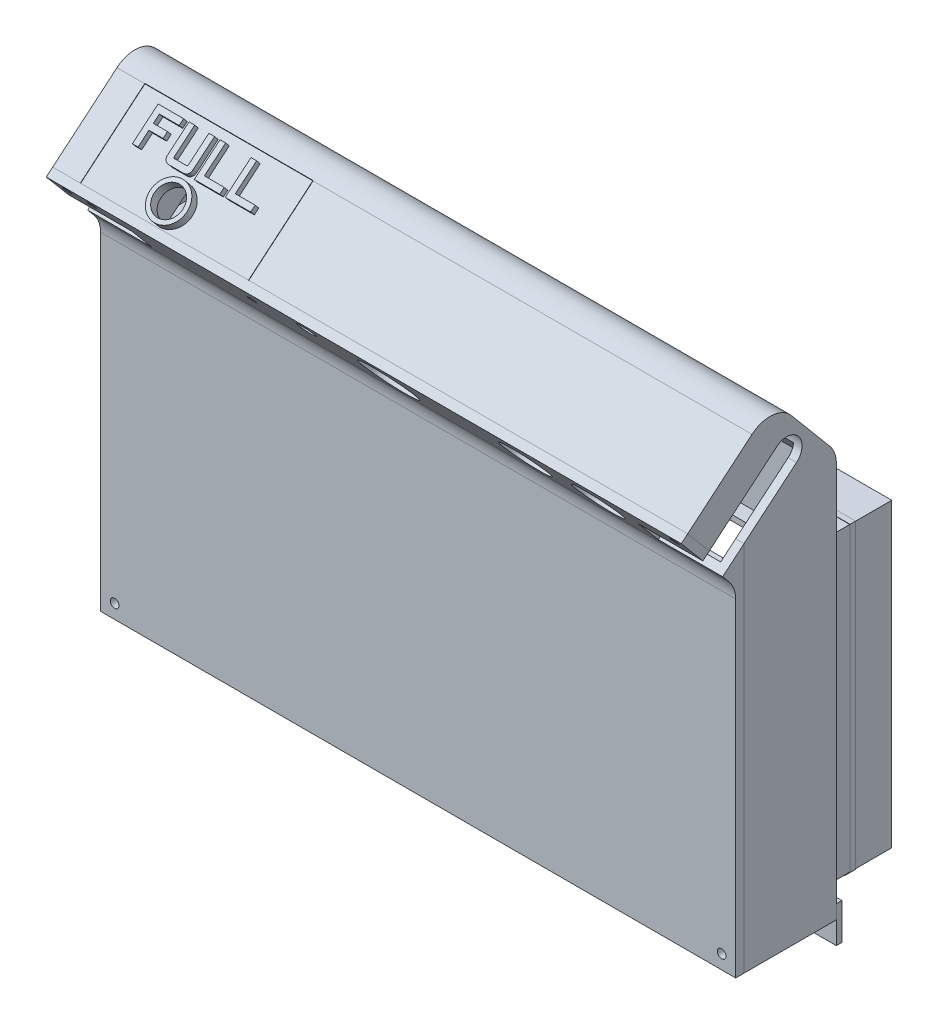
SolidWorks part; units mm, degrees
note: The reader was unsure of these and kept them because the rebuilt part matched: shared geometry of "스케치1<2>", "스케치2<3>", "스케치27<2>".
ref_plane "정면" through (0, 0, 0) normal (0, 0, 1) x (1, 0, 0)
ref_plane "윗면" through (0, 0, 0) normal (0, 1, 0) x (1, 0, 0)
ref_plane "우측면" through (0, 0, 0) normal (1, 0, 0) x (0, 0, -1)
sketch "스케치1" plane through (0, 0, 0) normal (0, 0, 1) x (1, 0, 0)
  line L5 (-104.9346, 72.3999) -> (122.0654, 72.3999)
  line L6 (-104.9346, 72.3999) -> (-104.9346, -72.6001)
  line L7 (-104.9346, -72.6001) -> (122.0654, -72.6001)
  line L8 (122.0654, 72.3999) -> (122.0654, -72.6001)
  line L9 (-101.9346, 69.3999) -> (119.0654, 69.3999)
  line L10 (-101.9346, 69.3999) -> (-101.9346, -69.6001)
  line L11 (-101.9346, -69.6001) -> (119.0654, -69.6001)
  line L12 (119.0654, 69.3999) -> (119.0654, -69.6001)
  dimension "D1" = 3
  dimension "D2" = 3
  dimension "D3" = 3
  dimension "D4" = 3
  dimension "D5" = 227
  dimension "D6" = 145
extrude "보스-돌출1" add sketch "스케치1" along normal blind 30
extrude "보스-돌출2" add sketch "스케치1<2>" against normal blind 3 contours L12 L9 L10 L11 | L8 L5 L6 L7 L9 L12 L11 L10
sketch "스케치1<2>" plane through (0, 0, 0) normal (0, 0, 1) x (1, 0, 0) same geometry as "스케치1"
sketch "스케치2" plane through (122.0654, 0, 0) normal (1, 0, 0) x (0, 0, -1)
  line L0 (3, 72.3999) -> (-19.4976, 99.2114)
  line L1 (-19.4976, 99.2114) -> (-21.7957, 97.2831)
  line L2 (-21.7957, 97.2831) -> (-0.9162, 72.3999)
  line L3 (-30, 72.3999) -> (3, 72.3999) construction
  line L4 (3, 72.3999) -> (3, -72.6001) construction
  line L5 (-11.2248, 76.1287) -> (-39.8222, 52.1327)
  line L6 (-39.8222, 52.1327) -> (-46.8928, 60.5592)
  line L7 (-46.8928, 60.5592) -> (-18.2955, 84.5552)
  line L8 (3, 72.3999) -> (-27.6418, 46.6884)
  line L9 (-19.4976, 99.2114) -> (-50.1393, 73.4999)
  line L10 (-50.1393, 73.4999) -> (-27.6418, 46.6884)
  circle A0 centre (-14.7602, 80.3419) radius 5.5
  line M5 (3, 72.3999) -> (-30, 72.3999)
  line M6 (-30, 72.3999) -> (-30, -72.6001)
  dimension "D3" = 11
  dimension "D5" = 17.5
  dimension "D6" = 8.5
  dimension "D7" = 5.5
  dimension "D1" = 3
  dimension "D2" = 140
  dimension "D4" = 35
  dimension "D8" = 11
  dimension "D9" = 40
  dimension "D10" = 90
extrude "보스-돌출3" add sketch "스케치2" against normal up to vertex contours A0 L2 L9 L10 L7 | L10 L8 L5 M6 M5 | A0 L5 L2 M5 | L1 L2 L0 M5
extrude "컷-돌출1" cut sketch "스케치2<3>" against normal up to vertex (227 mm away) contours A0 L7 L10 L5 M6 M5 | L5 M5 M6 | A0 | L10 L7 L6 L5 up to point (-104.9346, 99.2114, 19.4976)
sketch "스케치2<3>" plane through (122.0654, 0, 0) normal (1, 0, 0) x (0, 0, -1) same geometry as "스케치2"
sketch "스케치3" plane through (0, 41.0088, 34.4104) normal (0, -0.766, -0.6428) x (1, 0, 0)
  line L8 (-101.9346, -8.8359) -> (-101.9346, -44.1687)
  line L9 (-101.9346, -44.1687) -> (119.0654, -44.1687)
  line L10 (119.0654, -44.1687) -> (119.0654, -8.8359)
  line L11 (119.0654, -8.8359) -> (-101.9346, -8.8359)
  line L12 (-101.9346, -8.8359) -> (-101.9346, -44.1687)
  line L13 (-101.9346, -44.1687) -> (119.0654, -44.1687)
  line L14 (119.0654, -44.1687) -> (119.0654, -8.8359)
  line L15 (119.0654, -8.8359) -> (-101.9346, -8.8359)
  dimension "D1" = 0
extrude "컷-돌출2" cut sketch "스케치3" against normal blind 33
sketch "스케치4" plane through (0, 28.3911, -33.8352) normal (0, -0.6428, 0.766) x (1, 0, 0)
  line L0 (-101.9346, 86.5331) -> (-101.9346, 74.9777) construction
  line L1 (-81.9346, 86.5331) -> (99.0654, 86.5331)
  line L2 (-81.9346, 86.5331) -> (-81.9346, 53.5331)
  line L3 (-81.9346, 53.5331) -> (99.0654, 53.5331)
  line L4 (99.0654, 86.5331) -> (99.0654, 53.5331)
  line L5 (119.0654, 86.5331) -> (119.0654, 74.9777) construction
  dimension "D1" = 20
  dimension "D2" = 20
extrude "보스-돌출4" add sketch "스케치4" against normal up to vertex (4.6672 mm away) up to point (-104.9346, 99.2114, 19.4976)
sketch "스케치5" plane through (0, 5.6796, -6.7687) normal (0, -0.6428, 0.766) x (1, 0, 0)
  line L0 (122.0654, -36.3313) -> (122.0654, 65.5331) construction
  line L1 (-104.9346, 88.5331) -> (122.0654, 88.5331)
  line L2 (-104.9346, 88.5331) -> (-104.9346, 57.8136)
  line L3 (-104.9346, 57.8136) -> (122.0654, 57.8136)
  line L5 (-81.9346, 74.9777) -> (-81.9346, 67.0886) construction
  line L6 (-104.9346, 76.5331) -> (-81.9346, 76.5331)
  line L7 (-104.9346, 76.5331) -> (-104.9346, 65.5331)
  line L8 (-104.9346, 65.5331) -> (-81.9346, 65.5331)
  line L9 (-81.9346, 76.5331) -> (-81.9346, 65.5331)
  line L10 (99.0654, 67.0886) -> (99.0654, 74.9777) construction
  line L11 (122.0654, 76.5331) -> (99.0654, 76.5331)
  line L12 (122.0654, 76.5331) -> (122.0654, 65.5331)
  line L13 (122.0654, 65.5331) -> (99.0654, 65.5331)
  line L14 (99.0654, 76.5331) -> (99.0654, 65.5331)
  line L15 (-104.9346, 88.5331) -> (-104.9346, 76.5331)
  line L16 (-104.9346, 76.5331) -> (-81.9346, 76.5331)
  line L17 (-81.9346, 76.5331) -> (-81.9346, 65.5331)
  line L23 (-104.9346, 65.5331) -> (-104.9346, -36.3313) construction
  line L24 (-104.9346, 65.5331) -> (-81.9346, 65.5331)
  line L25 (122.0654, 76.5331) -> (99.0654, 76.5331)
  line L26 (99.0654, 65.5331) -> (99.0654, 76.5331)
  line L27 (99.0654, 65.5331) -> (122.0654, 65.5331)
  line L28 (122.0654, 88.5331) -> (122.0654, 57.8136)
  line L29 (119.0654, 76.5331) -> (122.0654, 76.5331) construction
  circle A0 centre (-99.9346, 84.5331) radius 1.55
  circle A1 centre (117.0654, 84.5331) radius 1.55
  line M3 (119.0654, 86.5331) -> (119.0654, 76.5331)
  line M4 (119.0654, 76.5331) -> (122.0654, 76.5331)
  line M5 (122.0654, 76.5331) -> (122.0654, 88.5331)
  line M6 (122.0654, 88.5331) -> (-104.9346, 88.5331)
  line M7 (-104.9346, 88.5331) -> (-104.9346, 76.5331)
  line M8 (-104.9346, 76.5331) -> (-101.9346, 76.5331)
  line M9 (-101.9346, 76.5331) -> (-101.9346, 86.5331)
  line M10 (-101.9346, 86.5331) -> (119.0654, 86.5331)
  dimension "D1" = 3.1
  dimension "D2" = 3.1
sketch "스케치6" plane through (0, 28.3911, -33.8352) normal (0, -0.6428, 0.766) x (1, 0, 0)
  line L1 (-101.9346, 86.5331) -> (-97.9346, 86.5331)
  line L2 (-101.9346, 86.5331) -> (-101.9346, 82.5331)
  line L3 (-101.9346, 82.5331) -> (-97.9346, 82.5331)
  line L4 (-97.9346, 86.5331) -> (-97.9346, 82.5331)
  line L5 (119.0654, 86.5331) -> (115.0654, 86.5331)
  line L6 (119.0654, 86.5331) -> (119.0654, 82.5331)
  line L7 (119.0654, 82.5331) -> (115.0654, 82.5331)
  line L8 (115.0654, 86.5331) -> (115.0654, 82.5331)
  circle A0 centre (-99.9346, 84.5331) radius 1.5
  circle A1 centre (117.0654, 84.5331) radius 1.5
  dimension "D3" = 3
  dimension "D4" = 2
  dimension "D5" = 2
  dimension "D8" = 3
  dimension "D9" = 2
  dimension "D10" = 2
  dimension "D1" = 4
  dimension "D2" = 4
  dimension "D6" = 4
  dimension "D7" = 4
extrude "보스-돌출6" add sketch "스케치5" along normal blind 3 separate body contours L28 L13 L14 L11 L6 L9 L8 L2 L3 A1 A0 M3 M10 M9 | M10 M3 M4 M5 M6 M7 M8 M9
extrude "보스-돌출7" add sketch "스케치6" along normal up to vertex
sketch "스케치7" plane through (0, 0, 30) normal (0, 0, 1) x (1, 0, 0)
  line L0 (-101.9346, -69.6001) -> (119.0654, -69.6001) construction
  line L1 (-104.9346, 52.2199) -> (122.0654, 52.2199)
  line L2 (-104.9346, 52.2199) -> (-104.9346, -72.6001)
  line L3 (-104.9346, -72.6001) -> (122.0654, -72.6001)
  line L4 (122.0654, 52.2199) -> (122.0654, -72.6001)
  line L5 (-101.9346, 60.3745) -> (-101.9346, -69.6001) construction
  line L6 (119.0654, -69.6001) -> (119.0654, 69.3999) construction
  line L7 (-101.9346, -69.6001) -> (119.0654, -69.6001) construction
  circle A0 centre (-99.9346, -67.6001) radius 1.55
  circle A1 centre (117.0654, -67.6001) radius 1.55
  dimension "D1" = 3.1
  dimension "D2" = 3.1
  dimension "D3" = 2
  dimension "D4" = 2
  dimension "D5" = 2
  dimension "D6" = 2
extrude "보스-돌출8" add sketch "스케치7" along normal blind 3
sketch "스케치8" plane through (-104.9346, 0, 0) normal (-1, 0, 0) x (0, 0, 1)
  line L0 (30, 60.3745) -> (37.6534, 53.9525)
  line L1 (37.6534, 53.9525) -> (34.1765, 49.8089)
  line L2 (37.6534, 53.9525) -> (33, 48.4069) construction
  line L3 (34.1765, 49.8089) -> (30, 52.2199)
  line L4 (30, 52.2199) -> (30, 60.3745)
sketch "스케치9" plane through (122.0654, 0, 0) normal (1, 0, 0) x (0, 0, -1)
  line L8 (-30, 60.3745) -> (-37.6534, 53.9525)
  line L9 (-37.6534, 53.9525) -> (-34.1765, 49.8089)
  line L10 (-34.1765, 49.8089) -> (-30, 52.2199)
  line L11 (-30, 52.2199) -> (-30, 60.3745)
  line L12 (-30, 60.3745) -> (-37.6534, 53.9525)
  line L13 (-37.6534, 53.9525) -> (-34.1765, 49.8089)
  line L14 (-34.1765, 49.8089) -> (-30, 52.2199)
  line L15 (-30, 52.2199) -> (-30, 60.3745)
  dimension "D1" = 0
extrude "보스-돌출9" add sketch "스케치9" against normal blind 3
extrude "보스-돌출10" add sketch "스케치8" against normal blind 3
sketch "스케치10" plane through (0, 0, -3) normal (0, 0, -1) x (-1, 0, 0)
  line L0 (104.9346, 72.3999) -> (-122.0654, 72.3999) construction
  line L1 (-117.0654, 42.3999) -> (99.9346, 42.3999)
  line L2 (-117.0654, 42.3999) -> (-117.0654, -67.6001)
  line L3 (-117.0654, -67.6001) -> (99.9346, -67.6001)
  line L4 (99.9346, 42.3999) -> (99.9346, -67.6001)
  line L5 (104.9346, -72.6001) -> (-122.0654, -72.6001) construction
  line L6 (-122.0654, 72.3999) -> (-122.0654, -72.6001) construction
  line L7 (104.9346, 72.3999) -> (104.9346, -72.6001) construction
  dimension "D1" = 30
  dimension "D2" = 5
  dimension "D3" = 5
  dimension "D4" = 5
extrude "컷-돌출3" cut sketch "스케치10" against normal blind 3
sketch "스케치11" plane through (0, 5.6796, -6.7687) normal (0, 0.6428, -0.766) x (-1, 0, 0)
  line L0 (-122.0654, 88.5331) -> (104.9346, 88.5331) construction
  line L3 (-122.0654, 76.5331) -> (-122.0654, 88.5331) construction
  circle A0 centre (-8.5654, 74.6831) radius 9.4
  circle A1 centre (-8.5654, 74.6831) radius 11.7
  circle A2 centre (-83.006, 73.9536) radius 8.1
  circle A3 centre (-57.006, 73.9536) radius 8.1
  dimension "D1" = 18.8
  dimension "D2" = 23.4
  dimension "D4" = 113.5
  dimension "D5" = 16.2
  dimension "D6" = 16.2
  dimension "D3" = 13.85
  dimension "D7" = 26
extrude "컷-돌출4" cut sketch "스케치11" against normal blind 3 contours A0 | A3 | A2
sketch "스케치13" plane through (0, 5.6796, -6.7687) normal (0, 0.6428, -0.766) x (-1, 0, 0)
  line L0 (-122.0654, 88.5331) -> (104.9346, 88.5331) construction
  line L2 (34.9346, 88.5331) -> (94.9346, 88.5331)
  line L3 (34.9346, 88.5331) -> (34.9346, 68.5331)
  line L4 (34.9346, 68.5331) -> (94.9346, 68.5331)
  line L5 (94.9346, 88.5331) -> (94.9346, 68.5331)
  line L6 (81.9346, 76.5331) -> (81.9346, 68.5331)
  line L7 (81.9346, 76.5331) -> (81.9346, 65.5331) construction
  line L8 (81.9346, 76.5331) -> (94.9346, 76.5331)
  line L9 (104.9346, 76.5331) -> (81.9346, 76.5331) construction
  circle A0 centre (16.4346, 81.5331) radius 3.05
  circle A1 centre (-8.5654, 74.6831) radius 9.4 construction
  circle A2 centre (64.9346, 78.5331) radius 3.5
  circle A3 centre (99.9346, 84.5331) radius 1.55 construction
  circle A4 centre (37.9346, 78.5331) radius 1.5
  circle A5 centre (91.9346, 83.5331) radius 1.5
  dimension "D1" = 6.1
  dimension "D2" = 7
  dimension "D3" = 25
  dimension "D4" = 7
  dimension "D6" = 10
  dimension "D7" = 30
  dimension "D10" = 3
  dimension "D11" = 3
  dimension "D12" = 3
  dimension "D13" = 3
  dimension "D14" = 5
  dimension "D15" = 10
  dimension "D5" = 20
  dimension "D8" = 5
  dimension "D9" = 60
extrude "컷-돌출5" cut sketch "스케치13" against normal blind 4 contours A0 | A4 | A5
sketch "스케치14" plane through (0, 5.6796, -6.7687) normal (0, 0.6428, -0.766) x (-1, 0, 0)
  line L0 (94.9346, 88.5331) -> (34.9346, 88.5331)
  line L1 (34.9346, 88.5331) -> (34.9346, 68.5331)
  line L2 (34.9346, 68.5331) -> (81.9346, 68.5331)
  line L3 (81.9346, 68.5331) -> (81.9346, 76.5331)
  line L4 (81.9346, 76.5331) -> (94.9346, 76.5331)
  line L5 (94.9346, 76.5331) -> (94.9346, 88.5331)
  line L6 (36.9346, 88.1331) -> (36.9346, 70.5331)
  line L7 (36.9346, 70.5331) -> (79.9346, 70.5331)
  line L8 (79.9346, 70.5331) -> (79.9346, 78.5331)
  line L9 (79.9346, 78.5331) -> (92.9346, 78.5331)
  line L10 (92.9346, 78.5331) -> (92.9346, 88.1331)
  line L11 (92.9346, 88.1331) -> (36.9346, 88.1331)
  line L13 (36.9346, 80.5331) -> (39.9346, 80.5331)
  line L14 (36.9346, 80.5331) -> (36.9346, 76.5331)
  line L15 (36.9346, 76.5331) -> (39.9346, 76.5331)
  line L16 (39.9346, 80.5331) -> (39.9346, 76.5331)
  line L17 (92.9346, 85.5331) -> (89.9346, 85.5331)
  line L18 (92.9346, 85.5331) -> (92.9346, 81.5331)
  line L19 (92.9346, 81.5331) -> (89.9346, 81.5331)
  line L20 (89.9346, 85.5331) -> (89.9346, 81.5331)
  line M10 (81.9346, 65.5331) -> (81.9346, 76.5331)
  line M11 (81.9346, 76.5331) -> (104.9346, 76.5331)
  line M13 (104.9346, 88.5331) -> (-122.0654, 88.5331)
  circle M20 centre (37.9346, 78.5331) radius 1.5
  circle M21 centre (91.9346, 83.5331) radius 1.5
  dimension "D1" = 2
  dimension "D2" = 0.4
  dimension "D3" = 2
  dimension "D4" = 2
  dimension "D5" = 2
  dimension "D6" = 2
  dimension "D7" = 2
  dimension "D8" = 2
  dimension "D9" = 2
  dimension "D10" = 2
  dimension "D11" = 2
  dimension "D12" = 2
extrude "보스-돌출11" add sketch "스케치14" along normal blind 30 separate body contours L16 L13 L6 L15 M20 | L5 L1 L2 L11 L10 L9 L8 L7 L6 M11 M13 M10 M21 M20 | L17 L20 L19 L10 M21
sketch "스케치15" plane through (0, 67.8203, 56.908) normal (0, 0.766, 0.6428) x (1, 0, 0)
  line L0 (122.0654, 8.8359) -> (-104.9346, 8.8359) construction
  line L1 (-34.8346, 38.9359) -> (-95.0346, 38.9359)
  line L2 (-34.8346, 38.9359) -> (-34.8346, 8.8359)
  line L3 (-34.8346, 8.8359) -> (-95.0346, 8.8359)
  line L4 (-95.0346, 38.9359) -> (-95.0346, 8.8359)
  line L5 (-94.9346, 38.8359) -> (-94.9346, 8.8359) construction
  line L6 (-94.9346, 38.8359) -> (-34.9346, 38.8359) construction
  line L7 (-34.9346, 38.8359) -> (-34.9346, 8.8359) construction
  dimension "D1" = 0.1
  dimension "D2" = 0.1
  dimension "D3" = 0.1
extrude "컷-돌출6" cut sketch "스케치15" against normal blind 2
sketch "스케치16" plane through (0, 24.9632, -29.75) normal (0, 0.6428, -0.766) x (-1, 0, 0)
  line L12 (81.9346, 76.5331) -> (94.9346, 76.5331)
  line L13 (94.9346, 76.5331) -> (94.9346, 88.5331)
  line L14 (94.9346, 88.5331) -> (34.9346, 88.5331)
  line L15 (34.9346, 88.5331) -> (34.9346, 68.5331)
  line L16 (34.9346, 68.5331) -> (81.9346, 68.5331)
  line L17 (81.9346, 68.5331) -> (81.9346, 76.5331)
  line L18 (81.9346, 76.5331) -> (94.9346, 76.5331)
  line L19 (94.9346, 76.5331) -> (94.9346, 88.5331)
  line L20 (94.9346, 88.5331) -> (34.9346, 88.5331)
  line L21 (34.9346, 88.5331) -> (34.9346, 68.5331)
  line L22 (34.9346, 68.5331) -> (81.9346, 68.5331)
  line L23 (81.9346, 68.5331) -> (81.9346, 76.5331)
  dimension "D1" = 0
extrude "보스-돌출12" add sketch "스케치16" against normal blind 2
sketch "스케치17" plane through (0, 52.4994, 44.0523) normal (0, -0.766, -0.6428) x (1, 0, 0)
  line L2 (-34.9346, -8.8359) -> (-81.9346, -8.8359) construction
  line L3 (-36.9346, -8.8359) -> (-79.9346, -8.8359)
  line L4 (-36.9346, -8.8359) -> (-36.9346, -36.8359)
  line L5 (-36.9346, -36.8359) -> (-79.9346, -36.8359)
  line L6 (-79.9346, -8.8359) -> (-79.9346, -36.8359)
  line L7 (-36.9346, -36.8359) -> (-36.9346, -8.8359) construction
  line L8 (-79.9346, -36.8359) -> (-79.9346, -8.8359) construction
  line L9 (-79.9346, -36.8359) -> (-36.9346, -36.8359) construction
extrude "컷-돌출7" cut sketch "스케치17" against normal blind 7
sketch "스케치21" plane through (0, 0, 30) normal (0, 0, -1) x (-1, 0, 0)
  line L0 (101.9346, 60.3745) -> (101.9346, -69.6001) construction
  line L1 (-119.0654, -69.6001) -> (-115.0654, -69.6001)
  line L2 (-119.0654, -69.6001) -> (-119.0654, -65.6001)
  line L3 (-119.0654, -65.6001) -> (-115.0654, -65.6001)
  line L4 (-115.0654, -69.6001) -> (-115.0654, -65.6001)
  line L5 (101.9346, -69.6001) -> (97.9346, -69.6001)
  line L6 (101.9346, -69.6001) -> (101.9346, -65.6001)
  line L7 (101.9346, -65.6001) -> (97.9346, -65.6001)
  line L8 (97.9346, -69.6001) -> (97.9346, -65.6001)
  line L10 (101.9346, -69.6001) -> (-119.0654, -69.6001) construction
  circle A0 centre (-117.0654, -67.6001) radius 1.55 construction
  circle A1 centre (99.9346, -67.6001) radius 1.55 construction
  circle A4 centre (-117.0654, -67.6001) radius 1.55
  circle A5 centre (-117.0654, -67.6001) radius 1.55
  circle A7 centre (99.9346, -67.6001) radius 1.55
  circle A8 centre (99.9346, -67.6001) radius 1.55
  dimension "D1" = 2
  dimension "D2" = 2
  dimension "D3" = 2
  dimension "D4" = 2
  dimension "D5" = 0
  dimension "D6" = 0
extrude "보스-돌출14" add sketch "스케치21" along normal up to vertex
sketch "스케치22" plane through (0, 0, -3) normal (0, 0, -1) x (-1, 0, 0)
  line L1 (-115.0654, -65.6001) -> (-119.2431, -65.6001)
  line L2 (-115.0654, -65.6001) -> (-115.0654, -70.1478)
  line L3 (-115.0654, -70.1478) -> (-119.2431, -70.1478)
  line L4 (-119.2431, -65.6001) -> (-119.2431, -70.1478)
  line L5 (97.9346, -65.6001) -> (101.5817, -65.6001)
  line L6 (97.9346, -65.6001) -> (97.9346, -69.4438)
  line L7 (97.9346, -69.4438) -> (101.5817, -69.4438)
  line L8 (101.5817, -65.6001) -> (101.5817, -69.4438)
extrude "보스-돌출15" add sketch "스케치22" against normal blind 7
sketch "스케치23" plane through (0, 67.8203, 56.908) normal (0, 0.766, 0.6428) x (1, 0, 0)
  line L8 (-94.9346, 8.8359) -> (-34.9346, 8.8359)
  line L9 (-34.9346, 8.8359) -> (-34.9346, 38.8359)
  line L10 (-34.9346, 38.8359) -> (-94.9346, 38.8359)
  line L11 (-94.9346, 38.8359) -> (-94.9346, 8.8359)
  line L12 (-94.9346, 8.8359) -> (-34.9346, 8.8359)
  line L13 (-34.9346, 8.8359) -> (-34.9346, 38.8359)
  line L14 (-34.9346, 38.8359) -> (-94.9346, 38.8359)
  line L15 (-94.9346, 38.8359) -> (-94.9346, 8.8359)
  dimension "D1" = 0
extrude "보스-돌출16" add sketch "스케치23" against normal blind 0.6
sketch "스케치26" plane through (0, 0, -15) normal (0, 0, -1) x (-1, 0, 0)
  line L16 (94.8346, -60.5001) -> (94.8346, 37.2999)
  line L17 (94.8346, 37.2999) -> (-111.9654, 37.2999)
  line L18 (-111.9654, 37.2999) -> (-111.9654, -60.5001)
  line L19 (-111.9654, -60.5001) -> (-109.9654, -60.5001)
  line L20 (-109.9654, -60.5001) -> (-109.9654, -62.5001)
  line L21 (-109.9654, -62.5001) -> (92.8346, -62.5001)
  line L22 (92.8346, -62.5001) -> (92.8346, -60.5001)
  line L23 (92.8346, -60.5001) -> (94.8346, -60.5001)
  line L24 (94.8346, -60.5001) -> (94.8346, 37.2999)
  line L25 (94.8346, 37.2999) -> (-111.9654, 37.2999)
  line L26 (-111.9654, 37.2999) -> (-111.9654, -60.5001)
  line L27 (-111.9654, -60.5001) -> (-109.9654, -60.5001)
  line L28 (-109.9654, -60.5001) -> (-109.9654, -62.5001)
  line L29 (-109.9654, -62.5001) -> (92.8346, -62.5001)
  line L30 (92.8346, -62.5001) -> (92.8346, -60.5001)
  line L31 (92.8346, -60.5001) -> (94.8346, -60.5001)
  line L40 (99.8346, -65.5001) -> (99.8346, 42.2999)
  line L41 (99.8346, 42.2999) -> (-116.9654, 42.2999)
  line L42 (-116.9654, 42.2999) -> (-116.9654, -65.5001)
  line L43 (-116.9654, -65.5001) -> (-114.9654, -65.5001)
  line L44 (-114.9654, -65.5001) -> (-114.9654, -67.5001)
  line L45 (-114.9654, -67.5001) -> (97.8346, -67.5001)
  line L46 (97.8346, -67.5001) -> (97.8346, -65.5001)
  line L47 (97.8346, -65.5001) -> (99.8346, -65.5001)
  line L48 (99.8346, -65.5001) -> (99.8346, 42.2999)
  line L49 (99.8346, 42.2999) -> (-116.9654, 42.2999)
  line L50 (-116.9654, 42.2999) -> (-116.9654, -65.5001)
  line L51 (-116.9654, -65.5001) -> (-114.9654, -65.5001)
  line L52 (-114.9654, -65.5001) -> (-114.9654, -67.5001)
  line L53 (-114.9654, -67.5001) -> (97.8346, -67.5001)
  line L54 (97.8346, -67.5001) -> (97.8346, -65.5001)
  line L55 (97.8346, -65.5001) -> (99.8346, -65.5001)
  dimension "D1" = 5
  dimension "D2" = 0
extrude "보스-돌출18" add sketch "스케치26" against normal blind 2
sketch "스케치27" plane through (0, 0, -3) normal (0, 0, -1) x (-1, 0, 0)
  line L0 (-122.0654, 72.3999) -> (-122.0654, -72.6001) construction
  line L1 (-122.0654, -67.6001) -> (104.9346, -67.6001)
  line L2 (-122.0654, -67.6001) -> (-122.0654, -80.6001)
  line L3 (-122.0654, -80.6001) -> (104.9346, -80.6001)
  line L4 (104.9346, -67.6001) -> (104.9346, -80.6001)
  line L5 (104.9346, -72.6001) -> (-122.0654, -72.6001) construction
  line L6 (-115.0654, -67.6001) -> (97.9346, -67.6001) construction
  line L7 (104.9346, 72.3999) -> (104.9346, -72.6001) construction
  circle A0 centre (-120.0654, -70.6001) radius 1.5
  circle A1 centre (102.9346, -70.6001) radius 1.5
  dimension "D3" = 3
  dimension "D4" = 2
  dimension "D5" = 2
  dimension "D6" = 3
  dimension "D7" = 2
  dimension "D8" = 2
  dimension "D1" = 8
  dimension "D2" = 0
extrude "보스-돌출19" add sketch "스케치27" along normal blind 2 separate body
extrude "컷-돌출9" cut sketch "스케치27<2>" against normal blind 10 contours A0 | A1
sketch "스케치27<2>" plane through (0, 0, -3) normal (0, 0, -1) x (-1, 0, 0) same geometry as "스케치27"
sketch "스케치28" plane through (0, 0, 30) normal (0, 0, -1) x (-1, 0, 0)
  line L0 (99.9346, 42.3999) -> (-117.0654, 42.3999) construction
  line L1 (-119.0654, 42.1999) -> (-114.0654, 42.1999)
  line L2 (-119.0654, 42.1999) -> (-119.0654, 37.1999)
  line L3 (-119.0654, 37.1999) -> (-114.0654, 37.1999)
  line L4 (-114.0654, 42.1999) -> (-114.0654, 37.1999)
  line L6 (-119.0654, -65.6001) -> (-119.0654, 60.3745) construction
  line L9 (96.9346, 42.1999) -> (101.9346, 42.1999)
  line L10 (96.9346, 42.1999) -> (96.9346, 37.1999)
  line L11 (96.9346, 37.1999) -> (101.9346, 37.1999)
  line L12 (101.9346, 42.1999) -> (101.9346, 37.1999)
  line L13 (101.9346, 60.3745) -> (101.9346, -65.6001) construction
  line L14 (-119.0654, -65.6001) -> (-119.0654, 60.3745) construction
  line L15 (-119.0654, -65.4001) -> (-114.0654, -65.4001)
  line L16 (-119.0654, -65.4001) -> (-119.0654, -60.4001)
  line L17 (-119.0654, -60.4001) -> (-114.0654, -60.4001)
  line L18 (-114.0654, -65.4001) -> (-114.0654, -60.4001)
  line L19 (-115.0654, -65.6001) -> (-119.0654, -65.6001) construction
  line L20 (101.9346, -65.6001) -> (97.9346, -65.6001) construction
  line L21 (101.9346, -65.4001) -> (96.9346, -65.4001)
  line L22 (101.9346, -65.4001) -> (101.9346, -60.4001)
  line L23 (101.9346, -60.4001) -> (96.9346, -60.4001)
  line L24 (96.9346, -65.4001) -> (96.9346, -60.4001)
  dimension "D1" = 5
  dimension "D2" = 5
  dimension "D3" = 0.2
  dimension "D4" = 5
  dimension "D5" = 0.2
  dimension "D6" = 5
  dimension "D7" = 5
  dimension "D8" = 5
  dimension "D9" = 0.2
  dimension "D10" = 5
  dimension "D11" = 5
  dimension "D12" = 0.2
extrude "보스-돌출21" add sketch "스케치28" along normal blind 25
sketch "스케치24" plane through (0, 0, -3) normal (0, 0, -1) x (-1, 0, 0)
  line L54 (97.7346, -63.4001) -> (97.7346, 40.1999)
  line L55 (97.7346, 40.1999) -> (-114.8654, 40.1999)
  line L56 (-114.8654, 40.1999) -> (-114.8654, -63.4001)
  line L57 (-114.8654, -63.4001) -> (-112.8654, -63.4001)
  line L58 (-112.8654, -63.4001) -> (-112.8654, -65.4001)
  line L59 (-112.8654, -65.4001) -> (95.7346, -65.4001)
  line L60 (95.7346, -65.4001) -> (95.7346, -63.4001)
  line L61 (95.7346, -63.4001) -> (97.7346, -63.4001)
  line L62 (99.7346, -65.4001) -> (99.7346, 42.1999)
  line L63 (97.7346, -65.4001) -> (99.7346, -65.4001)
  line L64 (97.7346, -67.4001) -> (97.7346, -65.4001)
  line L65 (-114.8654, -67.4001) -> (97.7346, -67.4001)
  line L66 (-114.8654, -65.4001) -> (-114.8654, -67.4001)
  line L67 (-116.8654, -65.4001) -> (-114.8654, -65.4001)
  line L68 (-116.8654, 42.1999) -> (-116.8654, -65.4001)
  line L69 (99.7346, 42.1999) -> (-116.8654, 42.1999)
  line L70 (99.7346, -65.4001) -> (99.7346, 42.1999)
  line L71 (97.7346, -65.4001) -> (99.7346, -65.4001)
  line L72 (97.7346, -67.4001) -> (97.7346, -65.4001)
  line L73 (-114.8654, -67.4001) -> (97.7346, -67.4001)
  line L74 (-114.8654, -65.4001) -> (-114.8654, -67.4001)
  line L75 (-116.8654, -65.4001) -> (-114.8654, -65.4001)
  line L76 (-116.8654, 42.1999) -> (-116.8654, -65.4001)
  line L77 (99.7346, 42.1999) -> (-116.8654, 42.1999)
  dimension "D1" = 0.2
  dimension "D2" = 2
extrude "보스-돌출22" add sketch "스케치24" along normal blind 25 and the other way up to vertex (8 mm away) separate body other way up to point (114.0654, 37.1999, 5)
sketch "스케치29" plane through (0, 0, -28) normal (0, 0, -1) x (-1, 0, 0)
  line L16 (90.7346, -58.4001) -> (92.7346, -58.4001)
  line L17 (92.7346, -58.4001) -> (92.7346, 35.1999)
  line L18 (92.7346, 35.1999) -> (-109.8654, 35.1999)
  line L19 (-109.8654, 35.1999) -> (-109.8654, -58.4001)
  line L20 (-109.8654, -58.4001) -> (-107.8654, -58.4001)
  line L21 (-107.8654, -58.4001) -> (-107.8654, -60.4001)
  line L22 (-107.8654, -60.4001) -> (90.7346, -60.4001)
  line L23 (90.7346, -60.4001) -> (90.7346, -58.4001)
  line L24 (90.7346, -58.4001) -> (92.7346, -58.4001)
  line L25 (92.7346, -58.4001) -> (92.7346, 35.1999)
  line L26 (92.7346, 35.1999) -> (-109.8654, 35.1999)
  line L27 (-109.8654, 35.1999) -> (-109.8654, -58.4001)
  line L28 (-109.8654, -58.4001) -> (-107.8654, -58.4001)
  line L29 (-107.8654, -58.4001) -> (-107.8654, -60.4001)
  line L30 (-107.8654, -60.4001) -> (90.7346, -60.4001)
  line L31 (90.7346, -60.4001) -> (90.7346, -58.4001)
  line L40 (97.7346, -65.4001) -> (99.7346, -65.4001)
  line L41 (99.7346, -65.4001) -> (99.7346, 42.1999)
  line L42 (99.7346, 42.1999) -> (-116.8654, 42.1999)
  line L43 (-116.8654, 42.1999) -> (-116.8654, -65.4001)
  line L44 (-116.8654, -65.4001) -> (-114.8654, -65.4001)
  line L45 (-114.8654, -65.4001) -> (-114.8654, -67.4001)
  line L46 (-114.8654, -67.4001) -> (97.7346, -67.4001)
  line L47 (97.7346, -67.4001) -> (97.7346, -65.4001)
  line L48 (97.7346, -65.4001) -> (99.7346, -65.4001)
  line L49 (99.7346, -65.4001) -> (99.7346, 42.1999)
  line L50 (99.7346, 42.1999) -> (-116.8654, 42.1999)
  line L51 (-116.8654, 42.1999) -> (-116.8654, -65.4001)
  line L52 (-116.8654, -65.4001) -> (-114.8654, -65.4001)
  line L53 (-114.8654, -65.4001) -> (-114.8654, -67.4001)
  line L54 (-114.8654, -67.4001) -> (97.7346, -67.4001)
  line L55 (97.7346, -67.4001) -> (97.7346, -65.4001)
  dimension "D1" = 7
  dimension "D2" = 0
extrude "보스-돌출23" add sketch "스케치29" against normal blind 2
fillet "필렛1" radius 10 1 edges at (8.5654, 72.3999, -3)
fillet "필렛2" radius 10 1 edges at (8.5654, 99.2114, 19.4976)
fillet "필렛3" radius 10 1 edges at (8.5654, 48.4069, 33)
sketch "스케치32" plane through (0, 67.3607, 56.5223) normal (0, -0.766, -0.6428) x (1, 0, 0)
  line L0 (-92.9346, -8.8359) -> (-36.9346, -8.8359) construction
  line L1 (-36.9346, -8.8359) -> (-36.9346, -36.8359) construction
  circle A0 centre (-66.9346, -15.8359) radius 5.1
  dimension "D1" = 10.2
  dimension "D2" = 7
  dimension "D3" = 30
extrude "컷-돌출10" cut sketch "스케치32" against normal blind 5
sketch "스케치33" plane through (0, 67.8203, 56.908) normal (0, 0.766, 0.6428) x (1, 0, 0)
  circle A1 centre (-66.9346, 15.8359) radius 6.6
  circle A2 centre (-66.9346, 15.8359) radius 5.1
  circle A3 centre (-66.9346, 15.8359) radius 5.1
  dimension "D1" = 0
  dimension "D2" = 1.5
extrude "보스-돌출26" add sketch "스케치33" along normal blind 3
sketch "스케치35" plane through (0, 67.8203, 56.908) normal (0, 0.766, 0.6428) x (1, 0, 0)
  text T0 "FULL" font "Air Force " height 12
extrude "보스-돌출27" add sketch "스케치35" along normal blind 2 separate body
